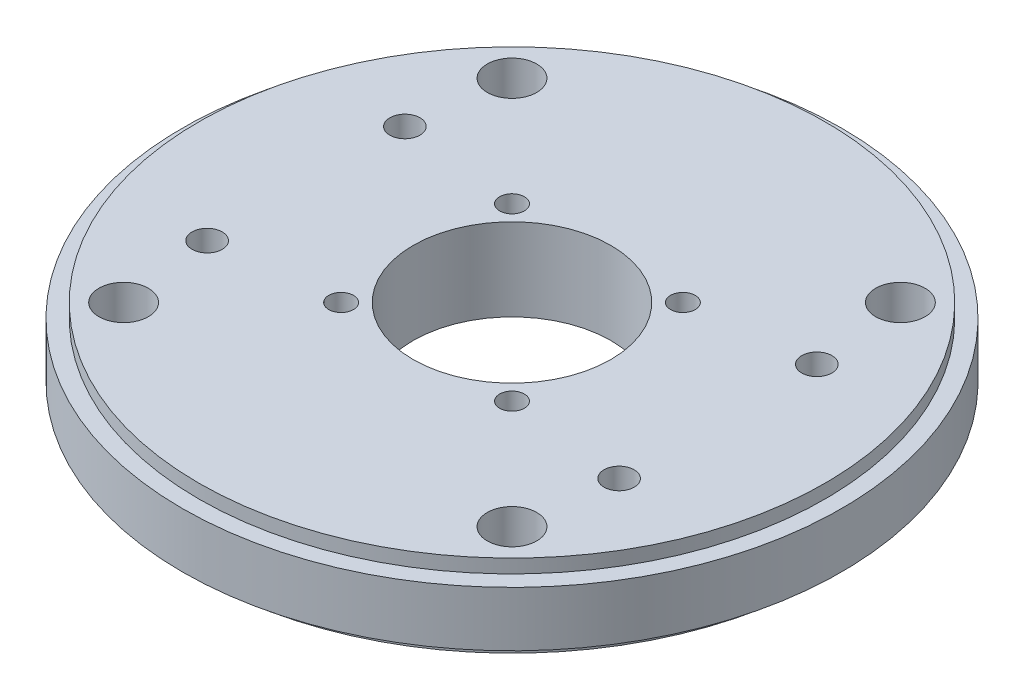
SolidWorks part; units mm, degrees
ref_plane "Front Plane" through (0, 0, 0) normal (0, 0, 1) x (1, 0, 0)
ref_plane "Top Plane" through (0, 0, 0) normal (0, 1, 0) x (1, 0, 0)
ref_plane "Right Plane" through (0, 0, 0) normal (1, 0, 0) x (0, 0, -1)
sketch "Sketch1" plane through (0, 0, 0) normal (0, 1, 0) x (1, 0, 0)
  circle A0 centre (0, 0) radius 57
  circle A1 centre (0, 0) radius 60
  dimension "D1" = 120
  dimension "D2" = 114
extrude "Extrude4" add sketch "Sketch1" along normal mid plane 15 contours A0
extrude "Extrude5" add sketch "Sketch" along normal mid plane 10
sketch "Sketch" plane through (0, 0, 0) normal (0, 1, 0) x (1, 0, 0) same geometry as "Sketch1"
sketch "Sketch5" plane through (0, 0, 0) normal (0, 1, 0) x (1, 0, 0)
  circle A0 centre (0, 0) radius 18
  dimension "D1" = 36
extrude "Extrude6" cut sketch "Sketch5" against normal through all both and the other way through all
hole_wizard "Ø4.5 (4.5) Diameter Hole1" positions "Sketch10" profile "Sketch11" hole size "Ø4.5" standard "ISO" end condition through all
sketch "Sketch10" plane through (0, -7.5, 0) normal (0, -1, 0) x (-1, 0, 0)
  point P6 (15.5563, 15.5563)
sketch "Sketch11" plane through (-15.5563, -7.5, -15.5563) normal (1, 0, 0) x (0, 0, -1)
  line L0 (0, 0) -> (0, 15)
  line L1 (0, 15) -> (2.25, 15)
  line L2 (2.25, 15) -> (2.25, 0)
  line L5 (2.25, 0) -> (0, 0)
  line L11 (0, -6.35) -> (0, 107.95) construction
  dimension "Thru Hole Dia." = 4.5
  dimension "Thru Hole Depth" = 15
ref_axis "Axis1" through (0, -8.25, 0) along (0, 1, 0)
pattern_circular "CirPattern1" count 4 over 360 about axis through (0, -8.25, 0) along (0, 1, 0) of "Ø4.5 (4.5) Diameter Hole1"
hole_wizard "M5 Clearance Hole1" positions "Sketch14" profile "Sketch15" hole size "M5" standard "ISO" end condition through all
sketch "Sketch14" plane through (0, 7.5, 0) normal (0, 1, 0) x (1, 0, 0)
  point P0 (-37.5, 18)
  point P3 (-37.5, -18)
  point P6 (37.5, -18)
  point P9 (37.5, 18)
sketch "Sketch15" plane through (-37.5, 7.5, -18) normal (1, 0, 0) x (0, 0, 1)
  line L0 (0, 0) -> (0, 15)
  line L1 (0, 15) -> (2.75, 15)
  line L2 (2.75, 15) -> (2.75, 0)
  line L5 (2.75, 0) -> (0, 0)
  line L11 (0, -6.35) -> (0, 107.95) construction
  dimension "Thru Hole Dia." = 5.5
  dimension "Thru Hole Depth" = 15
hole_wizard "M8 Clearance Hole2" positions "Sketch21" profile "Sketch22" hole size "M8" standard "ISO" end condition through all
sketch "Sketch21" plane through (0, 7.5, 0) normal (0, 1, 0) x (1, 0, 0)
  line L1 (-707.1068, -707.1068) -> (707.1068, 707.1068) construction
  line L2 (0, -8.25) -> (0, 8.25) construction
  circle A1 centre (15.5563, 15.5563) radius 2.25 construction
  point P0 (-35.3553, -35.3553)
  dimension "D1" = 45
  dimension "D2" = 50
sketch "Sketch22" plane through (-35.3553, 7.5, 35.3553) normal (1, 0, 0) x (0, 0, 1)
  line L0 (0, 0) -> (0, 15)
  line L1 (0, 15) -> (4.5, 15)
  line L2 (4.5, 15) -> (4.5, 0)
  line L5 (4.5, 0) -> (0, 0)
  line L11 (0, -6.35) -> (0, 107.95) construction
  dimension "Thru Hole Dia." = 9
  dimension "Thru Hole Depth" = 15
pattern_circular "CirPattern3" count 4 over 360 about axis through (0, -8.25, 0) along (0, 1, 0) of "M8 Clearance Hole2"
